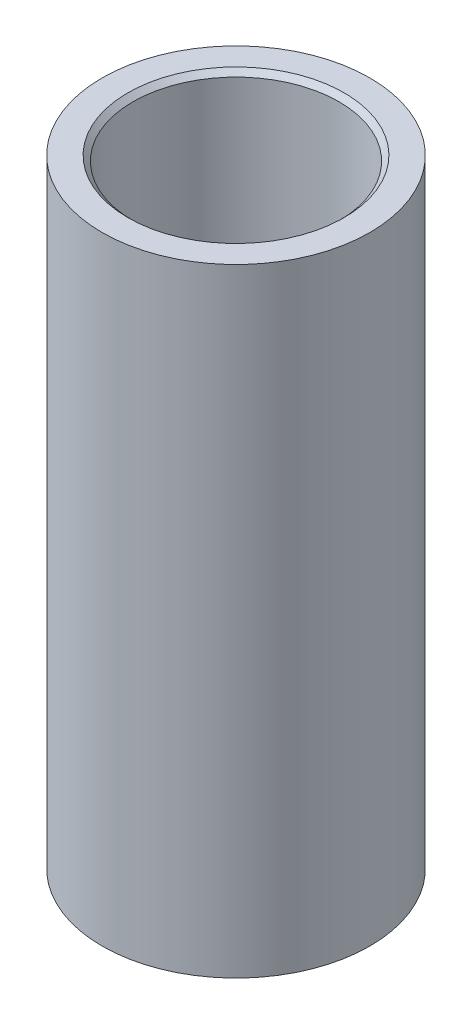
SolidWorks part; units mm, degrees
ref_plane "Front Plane" through (0, 0, 0) normal (0, 0, 1) x (1, 0, 0)
ref_plane "Top Plane" through (0, 0, 0) normal (0, 1, 0) x (1, 0, 0)
ref_plane "Right Plane" through (0, 0, 0) normal (1, 0, 0) x (0, 0, -1)
sketch "Sketch1" plane through (0, 0, 0) normal (0, 1, 0) x (1, 0, 0)
  circle A0 centre (0, 0) radius 10
  circle A1 centre (0, 0) radius 13
  dimension "D1" = 20
  dimension "D2" = 26
extrude "Boss-Extrude1" add sketch "Sketch1" along normal blind 60
chamfer "Chamfer1" distance 0.5 angle 45 2 edges at (0, 0, 10) (0, 60, 10)
